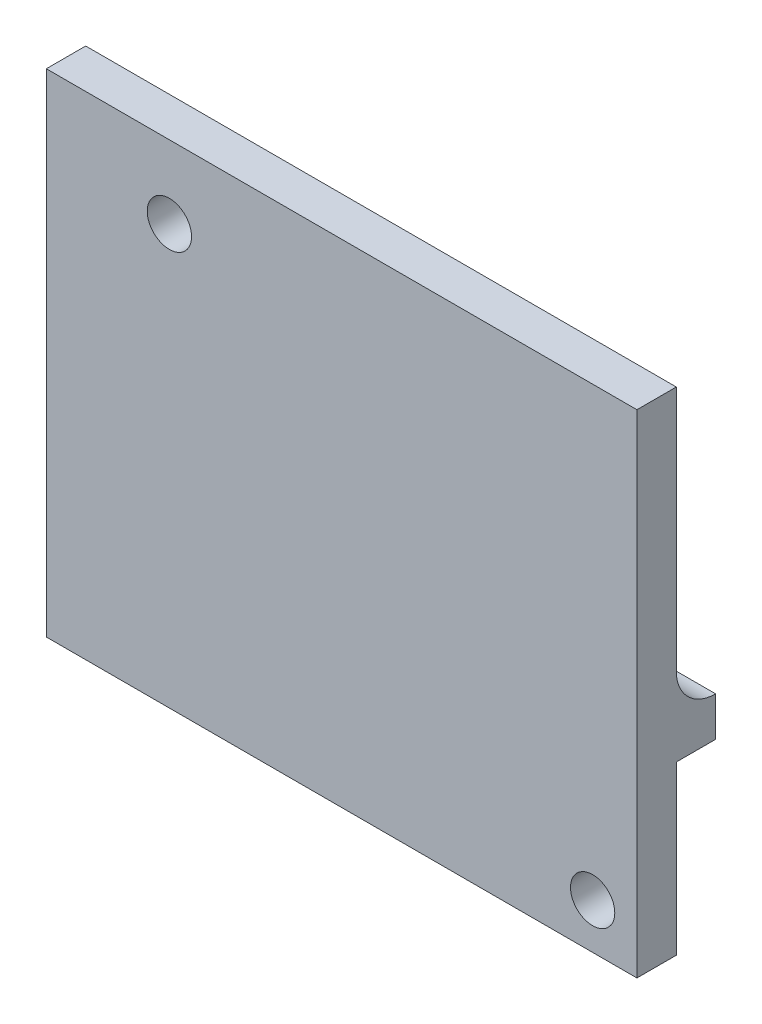
SolidWorks part; units mm, degrees
ref_plane "Płaszczyzna przednia" through (0, 0, 0) normal (0, 0, 1) x (1, 0, 0)
ref_plane "Płaszczyzna górna" through (0, 0, 0) normal (0, 1, 0) x (1, 0, 0)
ref_plane "Płaszczyzna prawa" through (0, 0, 0) normal (1, 0, 0) x (0, 0, -1)
sketch "Sketch1" plane through (0, 0, 0) normal (0, 0, 1) x (1, 0, 0)
  line L1 (0, 0) -> (60, 0)
  line L2 (0, 0) -> (0, 50)
  line L3 (0, 50) -> (60, 50)
  line L4 (60, 0) -> (60, 50)
  line L5 (0, 0) -> (60, 50) construction
  line L6 (0, 50) -> (60, 0) construction
  point P4 (30, 25)
  dimension "D1" = 60
  dimension "D2" = 50
extrude "Boss-Extrude1" add sketch "Sketch1" along normal blind 4
sketch "Sketch2" plane through (0, 0, 0) normal (0, 0, -1) x (-1, 0, 0)
  line L0 (0, 50) -> (0, 0) construction
  line L1 (0, 21) -> (-60, 21)
  line L2 (0, 21) -> (0, 17)
  line L3 (0, 17) -> (-60, 17)
  line L4 (-60, 21) -> (-60, 17)
  line L5 (0, 21) -> (-60, 17) construction
  line L6 (0, 17) -> (-60, 21) construction
  line L7 (-60, 0) -> (-60, 50) construction
  line L9 (0, 0) -> (-60, 0) construction
  point P4 (-30, 19)
  dimension "D1" = 17
  dimension "D2" = 4
extrude "Boss-Extrude2" add sketch "Sketch2" along normal blind 4
sketch "Sketch3" plane through (0, 0, 4) normal (0, 0, 1) x (1, 0, 0)
  circle A0 centre (12.5, 42.6) radius 2.25
  circle A1 centre (55.5, 4.6) radius 2.25
  dimension "D1" = 4.5
  dimension "D2" = 4.5
extrude "Cut-Extrude1" cut sketch "Sketch3" against normal blind 4
fillet "Fillet1" radius 4 1 edges at (30, 21, 0)
